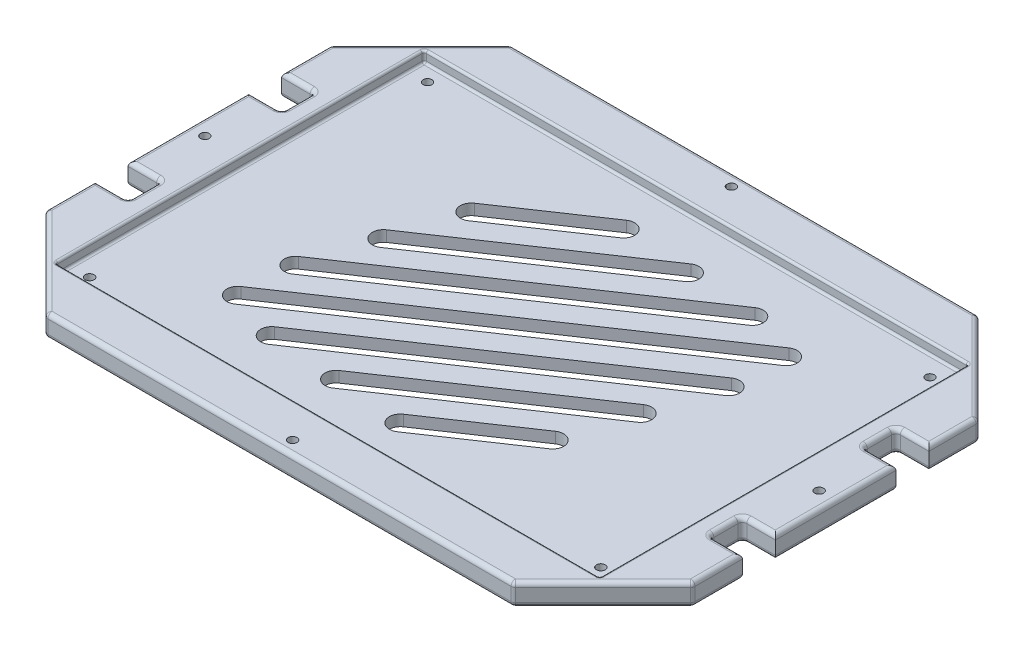
SolidWorks part; units mm, degrees
material "ABS"
ref_plane "Front Plane" through (0, 0, 0) normal (0, 0, 1) x (1, 0, 0)
ref_plane "Top Plane" through (0, 0, 0) normal (0, 1, 0) x (1, 0, 0)
ref_plane "Right Plane" through (0, 0, 0) normal (1, 0, 0) x (0, 0, -1)
sketch "Sketch1" plane through (0, 0, 0) normal (0, 1, 0) x (1, 0, 0)
  line L0 (110.0381, -116.5) -> (156, -70.5381) construction
  line L1 (-55, 0) -> (55, 0) construction
  line L2 (-147.5, -64.8959) -> (-147.5, 64.8959)
  line L3 (-147.5, -106) -> (-106.3959, -106) construction
  line L4 (147.5, -64.8959) -> (147.5, 64.8959)
  line L5 (-147.5, -106) -> (147.5, 106) construction
  line L6 (-147.5, 106) -> (147.5, -106) construction
  line L7 (-110.0381, -116.5) -> (110.0381, -116.5) construction
  line L8 (-156, -70.5381) -> (-156, 70.5381) construction
  line L9 (-110.0381, 116.5) -> (110.0381, 116.5) construction
  line L10 (156, -70.5381) -> (156, 70.5381) construction
  line L11 (-156, -116.5) -> (156, 116.5) construction
  line L12 (-156, 116.5) -> (156, -116.5) construction
  line L14 (110.0381, -116.5) -> (156, -116.5) construction
  line L15 (156, -116.5) -> (156, -70.5381) construction
  line L16 (147.5, -106) -> (147.5, -64.8959) construction
  line L17 (106.3959, 106) -> (147.5, 64.8959)
  line L18 (110.0381, 116.5) -> (156, 70.5381) construction
  line L20 (106.3959, -106) -> (147.5, -106) construction
  line L21 (106.3959, -106) -> (147.5, -64.8959)
  line L22 (106.3959, 106) -> (147.5, 106) construction
  line L29 (110.0381, 116.5) -> (156, 116.5) construction
  line L30 (156, 70.5381) -> (156, 116.5) construction
  line L31 (147.5, 106) -> (147.5, 64.8959) construction
  line L32 (0, -55) -> (0, 55) construction
  line L33 (-110.0381, -116.5) -> (-156, -70.5381) construction
  line L34 (-106.3959, -106) -> (-147.5, -64.8959)
  line L35 (-110.0381, 116.5) -> (-156, 70.5381) construction
  line L36 (-156, 116.5) -> (-110.0381, 116.5) construction
  line L37 (-156, 70.5381) -> (-156, 116.5) construction
  line L38 (-147.5, 64.8959) -> (-147.5, 106) construction
  line L39 (-106.3959, 106) -> (-147.5, 64.8959)
  line L40 (-106.3959, 106) -> (106.3959, 106)
  line L41 (-147.5, 106) -> (-106.3959, 106) construction
  line L43 (-147.5, -106) -> (-147.5, -64.8959) construction
  line L45 (-106.3959, -106) -> (106.3959, -106)
  line L48 (-156, -116.5) -> (-156, -70.5381) construction
  line L49 (-156, -116.5) -> (-110.0381, -116.5) construction
  line L51 (102.967, -109.4289) -> (148.9289, -63.467) construction
  point P0 (0, 0)
  point P5 (0, 0)
  dimension "D1" = 295
  dimension "D2" = 212
  dimension "D3" = 233
  dimension "D4" = 312
  dimension "D5" = 65
  dimension "D6" = 45
  dimension "D7" = 10
extrude "Boss-Extrude1" add sketch "Sketch1" along normal mid plane 10 contours L34 L45 L21 L4 L17 L40 L39 L2 | L9 L35 L8 L33 L7 L0 L10 L18 L45 L34 L2 L39 L40 L17 L4 L21 region at (0, 0, 0)
sketch "Sketch4" plane through (0, 5, 0) normal (0, 1, 0) x (1, 0, 0)
  line L0 (-5.5, 0) -> (5.5, 0) construction
  line L1 (-124, -84) -> (124, -84)
  line L2 (-124, -84) -> (-124, 84)
  line L3 (-124, 84) -> (124, 84)
  line L4 (124, -84) -> (124, 84)
  line L5 (-124, -84) -> (124, 84) construction
  line L6 (-124, 84) -> (124, -84) construction
  line L7 (-123, -82) -> (123, -82) construction
  line L8 (-123, -82) -> (-123, 82) construction
  line L9 (-123, 82) -> (123, 82) construction
  line L10 (123, -82) -> (123, 82) construction
  line L11 (-123, -82) -> (123, 82) construction
  line L12 (-123, 82) -> (123, -82) construction
  circle A0 centre (-115.5, 77) radius 2
  circle A1 centre (-115.5, -77) radius 2
  circle A2 centre (115.5, 75) radius 2
  circle A3 centre (115.5, -75) radius 2
  point P0 (0, 0)
  point P6 (0, 0)
  dimension "D5" = 7.5
  dimension "D7" = 4
  dimension "D8" = 4
  dimension "D9" = 4
  dimension "D1" = 168
  dimension "D2" = 248
  dimension "D3" = 164
  dimension "D4" = 246
  dimension "D6" = 7
  dimension "D10" = 7.5
  dimension "D11" = 7
  dimension "D12" = 7
extrude "Cut-Extrude2" cut sketch "Sketch4" against normal blind 5 contours L1 L4 L3 L2 A3 A2 A0 A1 | A0 | A2 | A3 | A1 region at (0, 5, 0) region at (-115.5, 5, -77) region at (-115.5, 5, 77) region at (115.5, 5, -75) region at (115.5, 5, 75)
sketch "Sketch5" plane through (0, 5, 0) normal (0, 1, 0) x (1, 0, 0)
  line L0 (-147.5, -64.8959) -> (-147.5, 64.8959) construction
  line L1 (-106.3959, 106) -> (106.3959, 106) construction
  line L2 (-106.3959, -106) -> (106.3959, -106) construction
  line L3 (147.5, -64.8959) -> (147.5, 64.8959) construction
  line L4 (0, -5.5) -> (0, 5.5) construction
  line L5 (-147.5, 42.5) -> (-132.5, 42.5)
  line L6 (-147.5, 42.5) -> (-147.5, 27.5)
  line L7 (-147.5, 27.5) -> (-132.5, 27.5)
  line L8 (-132.5, 42.5) -> (-132.5, 27.5)
  line L9 (-147.5, 42.5) -> (-132.5, 27.5) construction
  line L10 (-147.5, 27.5) -> (-132.5, 42.5) construction
  line L11 (-147.5, -27.5) -> (-132.5, -27.5)
  line L12 (-147.5, -27.5) -> (-147.5, -42.5)
  line L13 (-147.5, -42.5) -> (-132.5, -42.5)
  line L14 (-132.5, -27.5) -> (-132.5, -42.5)
  line L15 (-147.5, -27.5) -> (-132.5, -42.5) construction
  line L16 (-147.5, -42.5) -> (-132.5, -27.5) construction
  line L17 (147.5, -42.5) -> (132.5, -27.5) construction
  line L18 (147.5, -27.5) -> (132.5, -42.5) construction
  line L19 (147.5, 27.5) -> (132.5, 42.5) construction
  line L20 (147.5, 42.5) -> (132.5, 27.5) construction
  line L21 (132.5, -27.5) -> (132.5, -42.5) construction
  line L22 (147.5, -42.5) -> (132.5, -42.5) construction
  line L23 (147.5, -27.5) -> (147.5, -42.5) construction
  line L24 (147.5, -27.5) -> (132.5, -27.5) construction
  line L25 (132.5, 42.5) -> (132.5, 27.5) construction
  line L26 (147.5, 27.5) -> (132.5, 27.5) construction
  line L27 (147.5, 42.5) -> (147.5, 27.5) construction
  line L28 (147.5, 42.5) -> (132.5, 42.5) construction
  circle A0 centre (-140, 0) radius 2
  circle A1 centre (140, 0) radius 2 construction
  circle A2 centre (0, 100) radius 2
  circle A3 centre (0, -100) radius 2
  circle A4 centre (140, 0) radius 2 construction
  point P22 (-140, -35)
  point P26 (-140, 35)
  point P38 (140, 35)
  point P39 (140, -35)
  dimension "D1" = 4
  dimension "D4" = 4
  dimension "D2" = 7.5
  dimension "D3" = 6
  dimension "D5" = 6
  dimension "D6" = 7.5
  dimension "D7" = 15
  dimension "D8" = 15
  dimension "D9" = 35
  dimension "D10" = 35
  dimension "D11" = 15
  dimension "D12" = 15
extrude "Cut-Extrude3" cut sketch "Sketch5" against normal through all both and the other way through all
mirror "Mirror1" about plane through (0, 0, 0) normal (1, 0, 0) of "Cut-Extrude3"
extrude "Cut-Extrude4" cut sketch "Sketch4<3>" against normal through all both contours A1 | A2 | A3 | A0 region at (-115.5, 5, 77) region at (115.5, 5, -75) region at (115.5, 5, 75)
sketch "Sketch4<3>" plane through (0, 5, 0) normal (0, 1, 0) x (1, 0, 0) same geometry as "Sketch4"
fillet "Fillet1" radius 2 64 edges at (140, 5, 42.5) (140, 5, 27.5) (140, -5, 27.5) (140, -5, 42.5) (140, 5, -27.5) (140, 5, -42.5) (140, -5, -42.5) (140, -5, -27.5) (-140, -5, 42.5) (-140, 5, 42.5) (-140, -5, 27.5) (-140, 5, 27.5) (-140, -5, -27.5) (-140, 5, -27.5) (-140, -5, -42.5) (-140, 5, -42.5) (132.5, 5, 35) (132.5, 0, 27.5) (132.5, -5, 35) (132.5, 0, 42.5) (132.5, 5, -35) (132.5, 0, -42.5) (132.5, -5, -35) (132.5, 0, -27.5) (-132.5, 0, 42.5) (-132.5, -5, 35) (-132.5, 0, 27.5) (-132.5, 5, 35) (-132.5, 0, -27.5) (-132.5, -5, -35) (-132.5, 0, -42.5) (-132.5, 5, -35) (-126.948, -5, 85.448) (0, -5, 106) (126.948, -5, 85.448) (147.5, -5, -53.698) (147.5, -5, 0) (147.5, -5, 53.698) (126.948, -5, -85.448) (0, -5, -106) (-126.948, -5, -85.448) (-147.5, -5, -53.698) (-147.5, -5, 0) (-147.5, -5, 53.698) (-126.948, 5, 85.448) (0, 5, 106) (126.948, 5, 85.448) (147.5, 5, -53.698) (147.5, 5, 0) (147.5, 5, 53.698) (126.948, 5, -85.448) (0, 5, -106) (-126.948, 5, -85.448) (-147.5, 5, -53.698) (-147.5, 5, 0) (-147.5, 5, 53.698) (-147.5, 0, 64.8959) (-147.5, 0, -64.8959) (-106.3959, 0, -106) (106.3959, 0, -106) (147.5, 0, -64.8959) (-106.3959, 0, 106) (147.5, 0, 64.8959) (106.3959, 0, 106)
fillet "Fillet2" radius 1 12 edges at (0, 0, 84) (124, 0, 0) (0, 0, -84) (-124, 0, 0) (-124, 2.5, 84) (124, 2.5, 84) (0, 5, 84) (124, 2.5, -84) (-124, 2.5, -84) (124, 5, 0) (0, 5, -84) (-124, 5, 0)
sketch "Sketch6" plane through (0, 0, 0) normal (0, 1, 0) x (1, 0, 0)
  line L0 (-123, 0) -> (123, 0) construction
  line L1 (-123, 83) -> (-123, -83) construction
  line L2 (123, -83) -> (123, 83) construction
  line L3 (0, 83) -> (0, -84) construction
  line L4 (123, 83) -> (-123, 83) construction
  line L5 (123, -84) -> (-123, -84) construction
  line L6 (-108, 30) -> (-108, -30)
  line L7 (-108, -30) -> (-78, -30)
  line L8 (-78, -30) -> (-67.4204, 30)
  line L9 (-67.4204, 30) -> (-42.4204, 30)
  line L10 (-42.4204, 30) -> (-31.8408, -30)
  line L11 (-31.8408, -30) -> (-21.8408, -30)
  line L12 (-21.8408, -30) -> (-21.8408, 30)
  line L13 (-21.8408, 30) -> (-11.8408, 30)
  line L14 (-1.8408, 0) -> (8.1592, 0)
  line L15 (-11.8408, 30) -> (-1.8408, 0)
  line L16 (18.1592, 30) -> (8.1592, 0)
  line L17 (18.1592, 30) -> (28.1592, 30)
  line L18 (28.1592, 30) -> (28.1592, -30)
  line L20 (28.1592, -30) -> (38.1592, -30)
  line L21 (38.1592, -30) -> (38.1592, 30)
  line L22 (38.1592, 30) -> (68.1592, 30)
  line L23 (68.1592, 30) -> (68.1592, 0)
  line L24 (68.1592, 0) -> (58.1592, 0)
  line L25 (58.1592, 0) -> (63.1592, -30)
  line L26 (63.1592, -30) -> (108, -30)
  line L27 (108, -30) -> (108, -20)
  line L28 (108, -20) -> (78.1592, -20)
  line L29 (78.1592, -20) -> (78.1592, 30)
  line L30 (78.1592, 30) -> (108, 30)
  line L31 (-113, 30) -> (-113, -35)
  line L32 (-113, -35) -> (-73.8045, -35)
  line L33 (-73.8045, -35) -> (-63.2249, 25)
  line L34 (-63.2249, 25) -> (-46.6159, 25)
  line L35 (-46.6159, 25) -> (-36.0363, -35)
  line L36 (-36.0363, -35) -> (-16.8408, -35)
  line L37 (-16.8408, -35) -> (-16.8408, 25)
  line L38 (-16.8408, 25) -> (-15.4446, 25)
  line L39 (-15.4446, 25) -> (-5.4446, -5)
  line L40 (-5.4446, -5) -> (11.763, -5)
  line L41 (21.763, 25) -> (11.763, -5)
  line L42 (21.763, 25) -> (23.1592, 25)
  line L43 (23.1592, 25) -> (23.1592, -35)
  line L44 (23.1592, -35) -> (43.1592, -35)
  line L45 (43.1592, -35) -> (43.1592, 25)
  line L46 (43.1592, 25) -> (63.1592, 25)
  line L47 (63.1592, 25) -> (63.1592, 5)
  line L48 (63.1592, 5) -> (52.2569, 5)
  line L49 (52.2569, 5) -> (58.9236, -35)
  line L50 (58.9236, -35) -> (113, -35)
  line L51 (113, -35) -> (113, -15)
  line L52 (113, -15) -> (83.1592, -15)
  line L53 (83.1592, -15) -> (83.1592, 25)
  line L54 (83.1592, 25) -> (108, 25)
  line L55 (-113, 30) -> (-108, 30)
  line L56 (108, 30) -> (108, 25)
  line L57 (-70, 45) -> (70, 45) construction
  line L58 (-37.5, -70) -> (37.5, -70) construction
  text T0 "T-WORKS" font "Times New Roman" height 20
  text T1 "2025" font "Times New Roman" height 20
  point P14 (3.1592, 0)
  point P65 (0, 45)
  point P69 (0, -70)
  dimension "D1" = 60
  dimension "D2" = 30
  dimension "D3" = 100
  dimension "D4" = 100
  dimension "D5" = 15
  dimension "D6" = 30
  dimension "D7" = 25
  dimension "D8" = 10
  dimension "D9" = 50
  dimension "D10" = 10
  dimension "D11" = 25
  dimension "D12" = 10
  dimension "D13" = 10
  dimension "D14" = 30
  dimension "D15" = 10
  dimension "D16" = 30
  dimension "D17" = 25
  dimension "D18" = 10
  dimension "D19" = 15
  dimension "D20" = 10
  dimension "D22" = 45
  dimension "D23" = 140
  dimension "D24" = 35
  dimension "D25" = 75
  dimension "D21" = 5
extrude "Cut-Extrude5" [suppressed] cut sketch "Sketch6" against normal through all both and the other way through all
sketch "Sketch7" plane through (0, 0, 0) normal (0, 1, 0) x (1, 0, 0)
  line L0 (-123, -83) -> (123, 83) construction
  line L1 (123, -83) -> (123, 83) construction
  line L2 (-74.6034, -50.3421) -> (74.6034, 50.3421) construction
  line L3 (-77.4002, -46.1975) -> (71.8066, 54.4868)
  line L4 (-71.8066, -54.4868) -> (77.4002, 46.1975)
  line L5 (0, 0) -> (-41.3041, 61.2097) construction
  line L6 (0, 0) -> (37.8874, -56.1464) construction
  line L7 (-73.3567, -25.3732) -> (50.9824, 58.5303) construction
  line L8 (-76.1534, -21.2286) -> (48.1856, 62.675)
  line L9 (-70.5599, -29.5179) -> (53.7792, 54.3857)
  line L10 (-63.8206, 5.1892) -> (19.0721, 61.1249) construction
  line L11 (-66.6174, 9.3339) -> (16.2753, 65.2696)
  line L12 (-61.0238, 1.0446) -> (21.8688, 56.9803)
  line L13 (-54.2846, 35.7517) -> (-12.8383, 63.7195) construction
  line L14 (-57.0814, 39.8963) -> (-15.635, 67.8642)
  line L15 (-51.4878, 31.607) -> (-10.0415, 59.5749)
  line L16 (-50.9824, -58.5303) -> (73.3567, 25.3732) construction
  line L17 (-48.1856, -62.675) -> (76.1534, 21.2286)
  line L18 (-53.7792, -54.3857) -> (70.5599, 29.5179)
  line L19 (-19.0721, -61.1249) -> (63.8206, -5.1892) construction
  line L20 (-16.2753, -65.2696) -> (66.6174, -9.3339)
  line L21 (-21.8688, -56.9803) -> (61.0238, -1.0446)
  line L22 (12.8383, -63.7195) -> (54.2846, -35.7517) construction
  line L23 (15.635, -67.8642) -> (57.0814, -39.8963)
  line L24 (10.0415, -59.5749) -> (51.4878, -31.607)
  arc A0 (-76.1534, -21.2286) -> (-70.5599, -29.5179) centre (-73.3567, -25.3732) ccw
  arc A1 (-77.4002, -46.1975) -> (-71.8066, -54.4868) centre (-74.6034, -50.3421) ccw
  arc A2 (77.4002, 46.1975) -> (71.8066, 54.4868) centre (74.6034, 50.3421) ccw
  arc A3 (53.7792, 54.3857) -> (48.1856, 62.675) centre (50.9824, 58.5303) ccw
  arc A4 (-66.6174, 9.3339) -> (-61.0238, 1.0446) centre (-63.8206, 5.1892) ccw
  arc A5 (21.8688, 56.9803) -> (16.2753, 65.2696) centre (19.0721, 61.1249) ccw
  arc A6 (-57.0814, 39.8963) -> (-51.4878, 31.607) centre (-54.2846, 35.7517) ccw
  arc A7 (-10.0415, 59.5749) -> (-15.635, 67.8642) centre (-12.8383, 63.7195) ccw
  arc A8 (-48.1856, -62.675) -> (-53.7792, -54.3857) centre (-50.9824, -58.5303) cw
  arc A9 (70.5599, 29.5179) -> (76.1534, 21.2286) centre (73.3567, 25.3732) cw
  arc A10 (-16.2753, -65.2696) -> (-21.8688, -56.9803) centre (-19.0721, -61.1249) cw
  arc A11 (61.0238, -1.0446) -> (66.6174, -9.3339) centre (63.8206, -5.1892) cw
  arc A12 (15.635, -67.8642) -> (10.0415, -59.5749) centre (12.8383, -63.7195) cw
  arc A13 (51.4878, -31.607) -> (57.0814, -39.8963) centre (54.2846, -35.7517) cw
  point P2 (0, 0)
  point P18 (-11.1871, 16.5785)
  point P23 (-22.3743, 33.1571)
  point P30 (-33.5614, 49.7356)
  point P40 (11.1871, -16.5785)
  point P47 (22.3743, -33.1571)
  point P54 (33.5614, -49.7356)
  dimension "D1" = 180
  dimension "D2" = 10
  dimension "D3" = 90
  dimension "D4" = 10
  dimension "D5" = 150
  dimension "D6" = 100
  dimension "D7" = 20
  dimension "D8" = 20
  dimension "D9" = 20
  dimension "D10" = 10
  dimension "D11" = 10
  dimension "D12" = 50
extrude "Cut-Extrude6" cut sketch "Sketch7" against normal through all both and the other way through all
